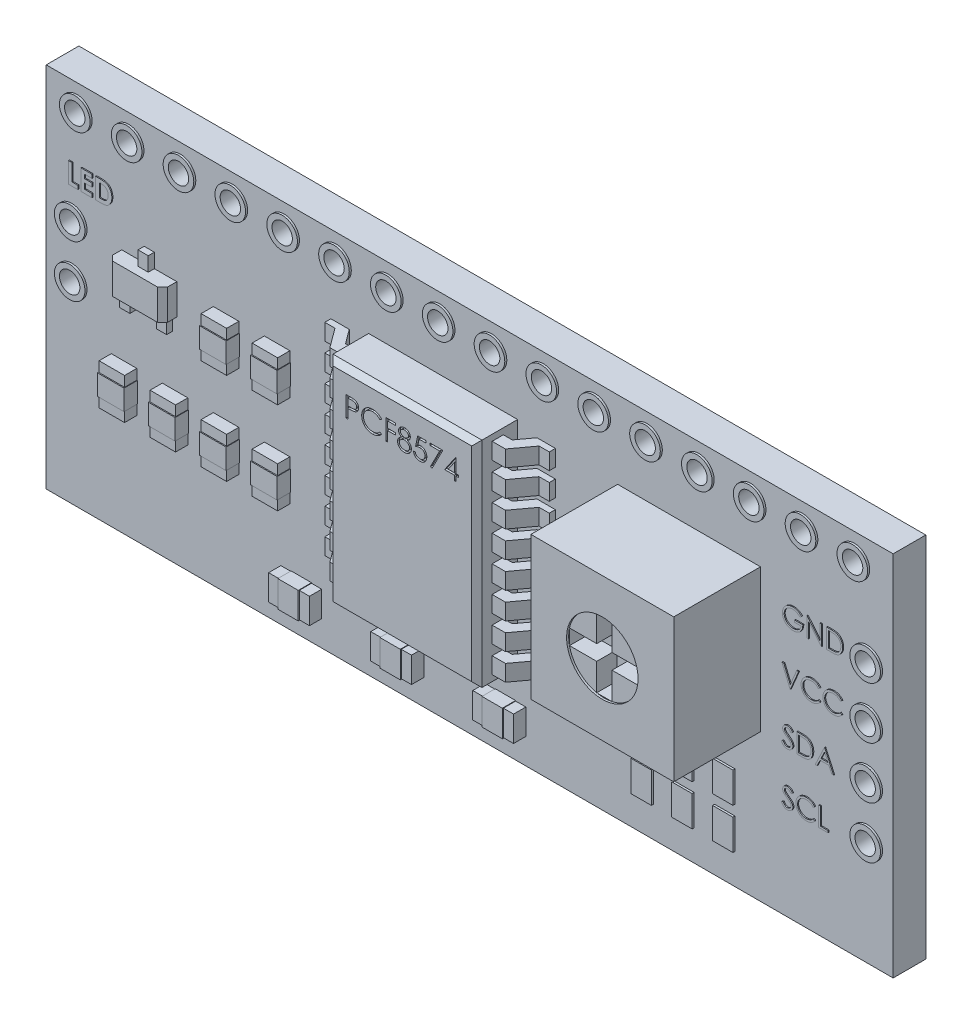
SolidWorks part; units mm, degrees
ref_plane "Front Plane" through (0, 0, 0) normal (0, 0, 1) x (1, 0, 0)
ref_plane "Top Plane" through (0, 0, 0) normal (0, 1, 0) x (1, 0, 0)
ref_plane "Right Plane" through (0, 0, 0) normal (1, 0, 0) x (0, 0, -1)
sketch "Sketch1" plane through (0, 0, 0) normal (0, 0, 1) x (1, 0, 0)
  line L1 (-20.75, 9) -> (20.75, 9)
  line L2 (-20.75, 9) -> (-20.75, -9)
  line L3 (-20.75, -9) -> (20.75, -9)
  line L4 (20.75, 9) -> (20.75, -9)
  line L5 (-20.75, 9) -> (20.75, -9) construction
  line L6 (-20.75, -9) -> (20.75, 9) construction
  point P0 (0, 0)
  dimension "D1" = 18
  dimension "D2" = 41.5
extrude "Boss-Extrude1" add sketch "Sketch1" along normal blind 1.6
sketch "Sketch2" plane through (0, 0, 1.6) normal (0, 0, 1) x (1, 0, 0)
  line L0 (20.75, 9) -> (-20.75, 9) construction
  line L1 (-20.75, 9) -> (-20.75, -9) construction
  circle A0 centre (-19.25, 7.75) radius 0.75
  dimension "D3" = 1.5
  dimension "D1" = 1.25
  dimension "D2" = 1.5
extrude "Boss-Extrude2" add sketch "Sketch2" along normal blind 0.1 and the other way blind 1.7
pattern_linear "LPattern1" count 16 spacing 2.54 along (1, 0, 0) of "Boss-Extrude2"
sketch "Sketch3" plane through (0, 0, 1.7) normal (0, 0, 1) x (1, 0, 0)
  line L2 (20.75, 9) -> (-20.75, 9) construction
  circle A0 centre (-19.25, 7.75) radius 0.5
  circle A1 centre (-16.7091, 7.75) radius 0.5
  circle A2 centre (-14.1682, 7.75) radius 0.5
  circle A3 centre (-11.6273, 7.75) radius 0.5
  circle A4 centre (-9.0864, 7.75) radius 0.5
  circle A5 centre (-6.5455, 7.75) radius 0.5
  circle A6 centre (-4.0045, 7.75) radius 0.5
  circle A7 centre (-1.4636, 7.75) radius 0.5
  circle A8 centre (1.0773, 7.75) radius 0.5
  circle A9 centre (3.6182, 7.75) radius 0.5
  circle A10 centre (6.1591, 7.75) radius 0.5
  circle A11 centre (8.7, 7.75) radius 0.5
  circle A12 centre (11.2409, 7.75) radius 0.5
  circle A13 centre (13.7818, 7.75) radius 0.5
  circle A14 centre (16.3227, 7.75) radius 0.5
  circle A15 centre (18.8636, 7.75) radius 0.5
  dimension "D1" = 1
  dimension "D3" = 1.25
  dimension "D2" = 16
extrude "Cut-Extrude1" cut sketch "Sketch3" against normal blind 1.8
sketch "Sketch4" plane through (0, 0, 1.6) normal (0, 0, 1) x (1, 0, 0)
  line L0 (20.75, 9) -> (-20.75, 9) construction
  line L1 (-4.95, 5.5) -> (2.35, 5.5)
  line L2 (-4.95, 5.5) -> (-4.95, -5)
  line L3 (-4.95, -5) -> (2.35, -5)
  line L4 (2.35, 5.5) -> (2.35, -5)
  line L5 (-20.75, 9) -> (-20.75, -9) construction
  dimension "D1" = 10.5
  dimension "D2" = 7.3
  dimension "D3" = 3.5
  dimension "D4" = 15.8
extrude "Boss-Extrude4" add sketch "Sketch4" along normal blind 2
sketch "Sketch5" plane through (0, 0, 1.6) normal (0, 0, 1) x (1, 0, 0)
  line L0 (-1.3, 5.5) -> (-1.3, -5) construction
  line L1 (2.35, 5.5) -> (-4.95, 5.5) construction
  line L2 (-4.95, -5) -> (2.35, -5) construction
  line L3 (-6.8, 3.1) -> (4.2, 3.1)
  line L4 (-6.8, 5.2) -> (4.2, 5.2)
  line L5 (-6.8, 5.2) -> (-6.8, 4.4)
  line L6 (-6.8, 4.4) -> (4.2, 4.4)
  line L7 (4.2, 5.2) -> (4.2, 4.4)
  line L8 (-6.8, 3.9) -> (-6.8, 3.1)
  line L9 (-6.8, 3.9) -> (4.2, 3.9)
  line L10 (4.2, 3.9) -> (4.2, 3.1)
  line L11 (-6.8, 1.8) -> (4.2, 1.8)
  line L12 (-6.8, 2.6) -> (-6.8, 1.8)
  line L13 (-6.8, 2.6) -> (4.2, 2.6)
  line L14 (4.2, 2.6) -> (4.2, 1.8)
  line L15 (-6.8, 0.5) -> (4.2, 0.5)
  line L16 (-6.8, 1.3) -> (-6.8, 0.5)
  line L17 (-6.8, 1.3) -> (4.2, 1.3)
  line L18 (4.2, 1.3) -> (4.2, 0.5)
  line L19 (-6.8, -0.8) -> (4.2, -0.8)
  line L20 (-6.8, 0) -> (-6.8, -0.8)
  line L21 (-6.8, 0) -> (4.2, 0)
  line L22 (4.2, 0) -> (4.2, -0.8)
  line L23 (-6.8, -2.1) -> (4.2, -2.1)
  line L24 (-6.8, -1.3) -> (-6.8, -2.1)
  line L25 (-6.8, -1.3) -> (4.2, -1.3)
  line L26 (4.2, -1.3) -> (4.2, -2.1)
  line L27 (-6.8, -3.4) -> (4.2, -3.4)
  line L28 (-6.8, -2.6) -> (-6.8, -3.4)
  line L29 (-6.8, -2.6) -> (4.2, -2.6)
  line L30 (4.2, -2.6) -> (4.2, -3.4)
  line L31 (-6.8, -4.7) -> (4.2, -4.7)
  line L32 (-6.8, -3.9) -> (-6.8, -4.7)
  line L33 (-6.8, -3.9) -> (4.2, -3.9)
  line L34 (4.2, -3.9) -> (4.2, -4.7)
  dimension "D1" = 11
  dimension "D2" = 5.5
  dimension "D3" = 0.3
  dimension "D4" = 0.8
  dimension "D5" = 8
extrude "Boss-Extrude6" add sketch "Sketch5" along normal blind 1.25
sketch "Sketch6" plane through (0, -4.7, 0) normal (0, -1, 0) x (1, 0, 0)
  line L0 (-6.8, 1.9) -> (-6.3, 1.9)
  line L1 (-6.8, 2.85) -> (-6.8, 1.6) construction
  line L2 (-6.3, 1.9) -> (-5.6, 2.85)
  line L3 (-6.8, 2.85) -> (-4.95, 2.85) construction
  line L4 (-5.6, 2.85) -> (-6.8, 2.85)
  line L5 (-6.8, 2.85) -> (-6.8, 1.9)
  line L6 (-4.95, 1.6) -> (-5.9, 1.6)
  line L7 (-6.8, 1.6) -> (-4.95, 1.6) construction
  line L8 (-5.9, 1.6) -> (-5.3842, 2.3)
  line L9 (-5.3842, 2.3) -> (-4.95, 2.3)
  line L10 (-4.95, 1.6) -> (-4.95, 2.85) construction
  line L11 (-4.95, 2.3) -> (-4.95, 1.6)
  line L12 (-1.3, 3.6) -> (-1.3, 1.6) construction
  line L13 (-4.95, 3.6) -> (2.35, 3.6) construction
  line L14 (-4.95, 1.6) -> (2.35, 1.6) construction
  line L15 (2.7842, 2.3) -> (2.35, 2.3)
  line L16 (2.35, 2.3) -> (2.35, 1.6)
  line L17 (2.35, 1.6) -> (3.3, 1.6)
  line L18 (3.3, 1.6) -> (2.7842, 2.3)
  line L19 (4.2, 1.9) -> (3.7, 1.9)
  line L20 (4.2, 2.85) -> (4.2, 1.9)
  line L21 (3, 2.85) -> (4.2, 2.85)
  line L22 (3.7, 1.9) -> (3, 2.85)
  dimension "D1" = 0.5
  dimension "D2" = 0.5
  dimension "D3" = 0.3
  dimension "D4" = 0.7
  dimension "D5" = 1.2
  dimension "D6" = 0.5
extrude "Cut-Extrude3" cut sketch "Sketch6" against normal blind 10
sketch "Sketch7" plane through (0, 0, 1.6) normal (0, 0, 1) x (1, 0, 0)
  line L0 (20.75, -9) -> (20.75, 9) construction
  line L2 (20.75, 9) -> (-20.75, 9) construction
  circle A0 centre (19.48, 3.75) radius 0.75
  circle A2 centre (19.48, 1.21) radius 0.75
  circle A3 centre (19.48, -1.33) radius 0.75
  circle A4 centre (19.48, -3.87) radius 0.75
  dimension "D1" = 1.5
  dimension "D2" = 1.27
  dimension "D3" = 5.25
  dimension "D4" = 4
extrude "Boss-Extrude8" add sketch "Sketch7" along normal blind 0.1 and the other way blind 1.7
sketch "Sketch8" plane through (0, 0, 1.7) normal (0, 0, 1) x (1, 0, 0)
  circle A0 centre (19.48, 3.75) radius 0.5
  circle A1 centre (19.48, 1.21) radius 0.5
  circle A2 centre (19.48, -1.33) radius 0.5
  circle A3 centre (19.48, -3.87) radius 0.5
  dimension "D1" = 1
  dimension "D2" = 4
extrude "Cut-Extrude4" cut sketch "Sketch8" against normal blind 1.8
chamfer "Chamfer1" distance 0.25 angle 45 4 edges at (2.35, 0.25, 3.6) (-4.95, 0.25, 3.6) (-1.3, 5.5, 3.6) (-1.3, -5, 3.6)
sketch "Sketch9" plane through (0, 0, 1.6) normal (0, 0, 1) x (1, 0, 0)
  line L0 (20.75, 9) -> (-20.75, 9) construction
  line L1 (-20.75, 9) -> (-20.75, -9) construction
  circle A0 centre (-19.5, 3) radius 0.75
  circle A1 centre (-19.5, 0.46) radius 0.75
  dimension "D1" = 1.5
  dimension "D2" = 1.5
  dimension "D3" = 2.54
  dimension "D4" = 6
  dimension "D5" = 1.25
  dimension "D6" = 1.25
extrude "Boss-Extrude9" add sketch "Sketch9" along normal blind 0.1 and the other way blind 1.7
sketch "Sketch10" plane through (0, 0, 1.7) normal (0, 0, 1) x (1, 0, 0)
  circle A0 centre (-19.5, 3) radius 0.5
  circle A1 centre (-19.5, 0.46) radius 0.5
  dimension "D1" = 1
  dimension "D2" = 1
extrude "Cut-Extrude5" cut sketch "Sketch10" against normal blind 1.8
sketch "Sketch11" plane through (0, 0, 1.6) normal (0, 0, 1) x (1, 0, 0)
  line L0 (20.75, -9) -> (20.75, 9) construction
  line L1 (7.25, 5.2) -> (14.25, 5.2)
  line L2 (7.25, 5.2) -> (7.25, -1.8)
  line L3 (7.25, -1.8) -> (14.25, -1.8)
  line L4 (14.25, 5.2) -> (14.25, -1.8)
  line L5 (20.75, 9) -> (-20.75, 9) construction
  dimension "D1" = 7
  dimension "D2" = 7
  dimension "D3" = 6.5
  dimension "D4" = 3.8
extrude "Boss-Extrude10" add sketch "Sketch11" along normal blind 4.25
sketch "Sketch12" plane through (0, 0, 5.85) normal (0, 0, 1) x (1, 0, 0)
  line L0 (7.25, 5.2) -> (7.25, -1.8) construction
  line L1 (14.25, 5.2) -> (7.25, 5.2) construction
  circle A0 centre (10.75, 1.7) radius 1.75
  point P4 (10.75, 5.2)
  dimension "D3" = 3.5
  dimension "D1" = 3.5
  dimension "D2" = 3.5
extrude "Cut-Extrude6" cut sketch "Sketch12" against normal blind 0.1
sketch "Sketch13" plane through (0, 0, 5.75) normal (0, 0, 1) x (1, 0, 0)
  line L0 (10.375, 1.325) -> (10.375, -0.0093)
  line L1 (10.375, 3.4093) -> (11.125, 3.4093)
  line L2 (10.375, 3.4093) -> (10.375, 2.075)
  line L3 (10.375, -0.0093) -> (11.125, -0.0093)
  line L4 (11.125, 3.4093) -> (11.125, 2.075)
  line L7 (9.0407, 2.075) -> (10.375, 2.075)
  line L8 (9.0407, 2.075) -> (9.0407, 1.325)
  line L9 (9.0407, 1.325) -> (10.375, 1.325)
  line L10 (12.4593, 2.075) -> (12.4593, 1.325)
  line L15 (11.125, 1.325) -> (11.125, -0.0093)
  line L16 (11.125, 2.075) -> (12.4593, 2.075)
  line L17 (11.125, 1.325) -> (12.4593, 1.325)
  circle A0 centre (10.75, 1.7) radius 1.75 construction
  point P0 (10.75, 1.7)
  point P8 (10.75, 1.7)
  dimension "D1" = 0.75
  dimension "D2" = 0.75
extrude "Cut-Extrude7" cut sketch "Sketch13" against normal blind 1
sketch "Sketch14" plane through (0, 0, 1.6) normal (0, 0, 1) x (1, 0, 0)
  line L0 (20.75, -9) -> (20.75, 9) construction
  line L1 (2.75, -6.5) -> (0.75, -6.5)
  line L2 (2.75, -6.5) -> (2.75, -7.75)
  line L3 (2.75, -7.75) -> (0.75, -7.75)
  line L4 (0.75, -6.5) -> (0.75, -7.75)
  line L5 (-2.25, -6.5) -> (-4.25, -6.5)
  line L6 (-2.25, -6.5) -> (-2.25, -7.75)
  line L7 (-2.25, -7.75) -> (-4.25, -7.75)
  line L8 (-4.25, -6.5) -> (-4.25, -7.75)
  line L9 (-7.25, -6.5) -> (-9.25, -6.5)
  line L10 (-7.25, -6.5) -> (-7.25, -7.75)
  line L11 (-7.25, -7.75) -> (-9.25, -7.75)
  line L12 (-9.25, -6.5) -> (-9.25, -7.75)
  line L13 (-20.75, -9) -> (20.75, -9) construction
  dimension "D1" = 2
  dimension "D2" = 1.25
  dimension "D3" = 2
  dimension "D4" = 2
  dimension "D5" = 3
  dimension "D6" = 3
  dimension "D7" = 18
  dimension "D8" = 1.25
  dimension "D9" = 1.25
  dimension "D10" = 1.25
  dimension "D11" = 1.25
  dimension "D12" = 1.25
extrude "Boss-Extrude11" add sketch "Sketch14" along normal blind 0.6
sketch "Sketch15" plane through (0, 0, 1.6) normal (0, 0, 1) x (1, 0, 0)
  line L0 (-12.5607, -3.6613) -> (-12.5607, -1.6613)
  line L1 (-8.8107, -3.6613) -> (-10.0607, -3.6613)
  line L2 (-8.8107, -3.6613) -> (-8.8107, -1.6613)
  line L3 (-8.8107, -1.6613) -> (-10.0607, -1.6613)
  line L4 (-10.0607, -3.6613) -> (-10.0607, -1.6613)
  line L5 (-11.3107, -3.6613) -> (-12.5607, -3.6613)
  line L6 (-11.3107, -3.6613) -> (-11.3107, -1.6613)
  line L7 (-11.3107, -1.6613) -> (-12.5607, -1.6613)
  line L8 (-15.0607, -3.6613) -> (-15.0607, -1.6613)
  line L9 (-13.8107, -3.6613) -> (-15.0607, -3.6613)
  line L10 (-13.8107, -3.6613) -> (-13.8107, -1.6613)
  line L11 (-13.8107, -1.6613) -> (-15.0607, -1.6613)
  line L12 (-17.5607, -3.6613) -> (-17.5607, -1.6613)
  line L13 (-16.3107, -3.6613) -> (-17.5607, -3.6613)
  line L14 (-16.3107, -3.6613) -> (-16.3107, -1.6613)
  line L15 (-16.3107, -1.6613) -> (-17.5607, -1.6613)
  dimension "D1" = 2
  dimension "D2" = 1.25
  dimension "D3" = 4
extrude "Boss-Extrude12" add sketch "Sketch15" along normal blind 0.6
sketch "Sketch16" plane through (0, 0, 1.6) normal (0, 0, 1) x (1, 0, 0)
  line L0 (-8.8107, -1.6613) -> (-10.0607, -1.6613) construction
  line L1 (-8.8107, 0.8387) -> (-10.0607, 0.8387)
  line L2 (-8.8107, 0.8387) -> (-8.8107, 2.8387)
  line L3 (-8.8107, 2.8387) -> (-10.0607, 2.8387)
  line L4 (-10.0607, 0.8387) -> (-10.0607, 2.8387)
  line L5 (-12.5607, 0.8387) -> (-12.5607, 2.8387)
  line L6 (-11.3107, 2.8387) -> (-12.5607, 2.8387)
  line L7 (-11.3107, 0.8387) -> (-11.3107, 2.8387)
  line L8 (-11.3107, 0.8387) -> (-12.5607, 0.8387)
  dimension "D1" = 2.5
  dimension "D3" = 1.25
  dimension "D4" = 0
  dimension "D5" = 2
  dimension "D2" = 2
extrude "Boss-Extrude13" add sketch "Sketch16" along normal blind 0.6
sketch "Sketch17" plane through (0, 0, 1.6) normal (0, 0, 1) x (1, 0, 0)
  line L0 (-20.75, -9) -> (20.75, -9) construction
  line L1 (8, -7.5) -> (9, -7.5)
  line L2 (8, -7.5) -> (8, -6)
  line L3 (8, -6) -> (9, -6)
  line L4 (9, -7.5) -> (9, -6)
  line L5 (8, -5.5) -> (9, -5.5)
  line L6 (8, -5.5) -> (8, -4)
  line L7 (8, -4) -> (9, -4)
  line L8 (9, -5.5) -> (9, -4)
  line L9 (20.75, -9) -> (20.75, 9) construction
  line L10 (10, -5.5) -> (10, -4)
  line L11 (10, -4) -> (11, -4)
  line L12 (11, -5.5) -> (11, -4)
  line L13 (10, -5.5) -> (11, -5.5)
  line L14 (10, -6) -> (11, -6)
  line L15 (11, -7.5) -> (11, -6)
  line L16 (10, -7.5) -> (10, -6)
  line L17 (10, -7.5) -> (11, -7.5)
  line L18 (12, -5.5) -> (12, -4)
  line L19 (12, -4) -> (13, -4)
  line L20 (13, -5.5) -> (13, -4)
  line L21 (12, -5.5) -> (13, -5.5)
  line L22 (12, -6) -> (13, -6)
  line L23 (13, -7.5) -> (13, -6)
  line L24 (12, -7.5) -> (12, -6)
  line L25 (12, -7.5) -> (13, -7.5)
  dimension "D1" = 1
  dimension "D2" = 1
  dimension "D3" = 0.5
  dimension "D4" = 1.5
  dimension "D5" = 1.5
  dimension "D6" = 1.5
  dimension "D7" = 12.75
  dimension "D8" = 3
extrude "Boss-Extrude14" add sketch "Sketch17" along normal blind 0.1
sketch "Sketch19" plane through (0, 0, 2.2) normal (0, 0, 1) x (1, 0, 0)
  line L0 (-9.25, -7.75) -> (-7.25, -7.75) construction
  line L1 (-8.75, -6.475) -> (-7.75, -6.475)
  line L2 (-8.75, -6.475) -> (-8.75, -7.775)
  line L3 (-8.75, -7.775) -> (-7.75, -7.775)
  line L4 (-7.75, -6.475) -> (-7.75, -7.775)
  line L5 (-8.75, -6.475) -> (-7.75, -7.775) construction
  line L6 (-8.75, -7.775) -> (-7.75, -6.475) construction
  line L7 (-9.25, -6.5) -> (-9.25, -7.75) construction
  line L8 (-3.75, -6.475) -> (-3.75, -7.775)
  line L9 (-3.75, -6.475) -> (-2.75, -6.475)
  line L10 (-2.75, -6.475) -> (-2.75, -7.775)
  line L11 (-3.75, -7.775) -> (-2.75, -7.775)
  line L12 (1.25, -6.475) -> (1.25, -7.775)
  line L13 (1.25, -6.475) -> (2.25, -6.475)
  line L14 (2.25, -6.475) -> (2.25, -7.775)
  line L15 (1.25, -7.775) -> (2.25, -7.775)
  point P0 (-8.25, -7.125)
  dimension "D1" = 1.3
  dimension "D2" = 0.025
  dimension "D3" = 1
  dimension "D4" = 0.5
  dimension "D5" = 3
extrude "Boss-Extrude16" add sketch "Sketch19" against normal blind 0.6 and the other way blind 0.05
sketch "Sketch20" plane through (0, 0, 2.2) normal (0, 0, 1) x (1, 0, 0)
  line L0 (-17.5607, -1.6613) -> (-17.5607, -3.6613) construction
  line L1 (-17.5857, -2.1613) -> (-16.2857, -2.1613)
  line L2 (-17.5857, -2.1613) -> (-17.5857, -3.1613)
  line L3 (-17.5857, -3.1613) -> (-16.2857, -3.1613)
  line L4 (-16.2857, -2.1613) -> (-16.2857, -3.1613)
  line L5 (-17.5857, -2.1613) -> (-16.2857, -3.1613) construction
  line L6 (-17.5857, -3.1613) -> (-16.2857, -2.1613) construction
  line L7 (-17.5607, -3.6613) -> (-16.3107, -3.6613) construction
  line L8 (-15.0857, -2.1613) -> (-13.7857, -2.1613)
  line L9 (-15.0857, -2.1613) -> (-15.0857, -3.1613)
  line L10 (-13.7857, -2.1613) -> (-13.7857, -3.1613)
  line L11 (-15.0857, -3.1613) -> (-13.7857, -3.1613)
  line L12 (-12.5857, -2.1613) -> (-11.2857, -2.1613)
  line L13 (-12.5857, -2.1613) -> (-12.5857, -3.1613)
  line L14 (-11.2857, -2.1613) -> (-11.2857, -3.1613)
  line L15 (-12.5857, -3.1613) -> (-11.2857, -3.1613)
  line L16 (-10.0857, -2.1613) -> (-8.7857, -2.1613)
  line L17 (-10.0857, -2.1613) -> (-10.0857, -3.1613)
  line L18 (-8.7857, -2.1613) -> (-8.7857, -3.1613)
  line L19 (-10.0857, -3.1613) -> (-8.7857, -3.1613)
  point P0 (-16.9357, -2.6613)
  dimension "D1" = 0.025
  dimension "D2" = 1.3
  dimension "D3" = 1
  dimension "D4" = 0.5
  dimension "D5" = 4
extrude "Boss-Extrude17" add sketch "Sketch20" against normal blind 0.6 and the other way blind 0.05
sketch "Sketch21" plane through (0, 0, 2.2) normal (0, 0, 1) x (1, 0, 0)
  line L0 (-12.5607, 2.8387) -> (-12.5607, 0.8387) construction
  line L1 (-12.5857, 2.3387) -> (-11.2857, 2.3387)
  line L2 (-12.5857, 2.3387) -> (-12.5857, 1.3387)
  line L3 (-12.5857, 1.3387) -> (-11.2857, 1.3387)
  line L4 (-11.2857, 2.3387) -> (-11.2857, 1.3387)
  line L5 (-12.5857, 2.3387) -> (-11.2857, 1.3387) construction
  line L6 (-12.5857, 1.3387) -> (-11.2857, 2.3387) construction
  line L7 (-12.5607, 0.8387) -> (-11.3107, 0.8387) construction
  line L8 (-10.0857, 2.3387) -> (-8.7857, 2.3387)
  line L9 (-10.0857, 2.3387) -> (-10.0857, 1.3387)
  line L10 (-8.7857, 2.3387) -> (-8.7857, 1.3387)
  line L11 (-10.0857, 1.3387) -> (-8.7857, 1.3387)
  point P0 (-11.9357, 1.8387)
  dimension "D1" = 1.3
  dimension "D2" = 0.025
  dimension "D3" = 0.5
  dimension "D4" = 1
  dimension "D5" = 2
extrude "Boss-Extrude18" add sketch "Sketch21" against normal blind 0.6 and the other way blind 0.05
sketch "Sketch23" plane through (0, 0, 1.6) normal (0, 0, 1) x (1, 0, 0)
  line L0 (-20.75, 9) -> (-20.75, -9) construction
  line L1 (-17.05, 3) -> (-14.35, 3)
  line L2 (-17.05, 3) -> (-17.05, 1.5)
  line L3 (-17.05, 1.5) -> (-14.35, 1.5)
  line L4 (-14.35, 3) -> (-14.35, 1.5)
  line L5 (-17.05, 3) -> (-14.35, 1.5) construction
  line L6 (-17.05, 1.5) -> (-14.35, 3) construction
  line L7 (20.75, 9) -> (-20.75, 9) construction
  point P0 (-15.7, 2.25)
  dimension "D1" = 2.7
  dimension "D2" = 1.5
  dimension "D3" = 3.7
  dimension "D4" = 6
extrude "Boss-Extrude19" add sketch "Sketch23" along normal blind 0.7
sketch "Sketch24" plane through (0, 0, 1.6) normal (0, 0, 1) x (1, 0, 0)
  line L0 (-14.35, 3) -> (-17.05, 3) construction
  line L1 (-15.95, 3) -> (-15.45, 3)
  line L2 (-15.95, 3) -> (-15.95, 3.7)
  line L3 (-15.95, 3.7) -> (-15.45, 3.7)
  line L4 (-15.45, 3) -> (-15.45, 3.7)
  line L5 (-17.05, 1.5) -> (-14.35, 1.5) construction
  line L6 (-16.85, 1.5) -> (-16.35, 1.5)
  line L7 (-16.85, 1.5) -> (-16.85, 0.8)
  line L8 (-16.85, 0.8) -> (-16.35, 0.8)
  line L9 (-16.35, 1.5) -> (-16.35, 0.8)
  line L10 (-17.05, 1.5) -> (-14.35, 1.5) construction
  line L11 (-14.55, 1.5) -> (-15.05, 1.5)
  line L12 (-14.55, 1.5) -> (-14.55, 0.8)
  line L13 (-14.55, 0.8) -> (-15.05, 0.8)
  line L14 (-15.05, 1.5) -> (-15.05, 0.8)
  line L15 (-17.05, 3) -> (-17.05, 1.5) construction
  line L16 (-14.35, 1.5) -> (-14.35, 3) construction
  dimension "D1" = 0.5
  dimension "D2" = 1.1
  dimension "D3" = 0.2
  dimension "D4" = 0.2
  dimension "D5" = 0.5
  dimension "D6" = 0.5
  dimension "D7" = 0.7
  dimension "D8" = 0.7
  dimension "D9" = 0.7
extrude "Boss-Extrude20" add sketch "Sketch24" along normal blind 0.3
chamfer "Chamfer2" distance 0.25 angle 45 2 edges at (-14.35, 2.25, 2.3) (-17.05, 2.25, 2.3)
sketch "Sketch25" plane through (0, 0, 1.7) normal (0, 0, 1) x (1, 0, 0)
  circle A0 centre (-19.25, 7.75) radius 0.5
  circle A1 centre (-16.71, 7.75) radius 0.5
  circle A2 centre (-14.17, 7.75) radius 0.5
  circle A3 centre (-11.63, 7.75) radius 0.5
  circle A4 centre (-9.09, 7.75) radius 0.5
  circle A5 centre (-6.55, 7.75) radius 0.5
  circle A6 centre (-4.01, 7.75) radius 0.5
  circle A7 centre (-1.47, 7.75) radius 0.5
  circle A8 centre (1.07, 7.75) radius 0.5
  circle A9 centre (3.61, 7.75) radius 0.5
  circle A10 centre (6.15, 7.75) radius 0.5
  circle A11 centre (8.69, 7.75) radius 0.5
  circle A12 centre (11.23, 7.75) radius 0.5
  circle A13 centre (13.77, 7.75) radius 0.5
  circle A14 centre (16.31, 7.75) radius 0.5
  circle A15 centre (18.85, 7.75) radius 0.5
  point P3 (0, 0)
  dimension "D1" = 16
sketch "Sketch27" plane through (0, 0, -0.1) normal (0, 0, -1) x (-1, 0, 0)
  line L0 (20.75, 9) -> (20.75, -9) construction
  line L1 (-20.75, 9) -> (20.75, 9)
  line L2 (-20.75, 9) -> (-20.75, 6.5)
  line L3 (-20.75, 6.5) -> (20.75, 6.5)
  line L4 (20.75, 9) -> (20.75, 6.5)
  dimension "D1" = 2.5
sketch "Sketch28" plane through (0, 0, 1.6) normal (0, 0, 1) x (1, 0, 0)
  text T0 "<b>LED</b>" font "Century Gothic" height 1
extrude "Boss-Extrude24" add sketch "Sketch28" along normal blind 0.05
sketch "Sketch29" plane through (0, 0, 1.6) normal (0, 0, 1) x (1, 0, 0)
  text T0 "GND\r\nVCC\r\nSDA\r\nSCL" font "Century Gothic" height 0.95
extrude "Boss-Extrude25" add sketch "Sketch29" along normal blind 0.05
sketch "Sketch30" plane through (0, 0, 3.6) normal (0, 0, 1) x (1, 0, 0)
  text T0 "PCF8574" font "Century Gothic" height 1
extrude "Cut-Extrude8" cut sketch "Sketch30" against normal blind 0.1
sketch "Sketch31" plane through (0, 0, 1.7) normal (0, 0, 1) x (1, 0, 0)
  line L1 (-20.75, 4.5) -> (-18.25, 4.5)
  line L2 (-20.75, 4.5) -> (-20.75, -1.04)
  line L3 (-20.75, -1.04) -> (-18.25, -1.04)
  line L4 (-18.25, 4.5) -> (-18.25, -1.04)
  line L5 (18.23, 5.25) -> (20.73, 5.25)
  line L6 (18.23, 5.25) -> (18.23, -5.37)
  line L7 (18.23, -5.37) -> (20.73, -5.37)
  line L8 (20.73, 5.25) -> (20.73, -5.37)
  circle A0 centre (-19.5, 3) radius 0.5 construction
  circle A1 centre (-19.5, 0.46) radius 0.5 construction
  circle A2 centre (19.48, 1.21) radius 0.5 construction
  circle A3 centre (19.48, 3.75) radius 0.5 construction
  circle A4 centre (19.48, -3.87) radius 0.5 construction
  dimension "D6" = 1.25
  dimension "D7" = 1.5
  dimension "D1" = 1.5
  dimension "D2" = 2.5
  dimension "D3" = 1.25
  dimension "D4" = 1.5
  dimension "D5" = 2.5
  dimension "D8" = 1.5
